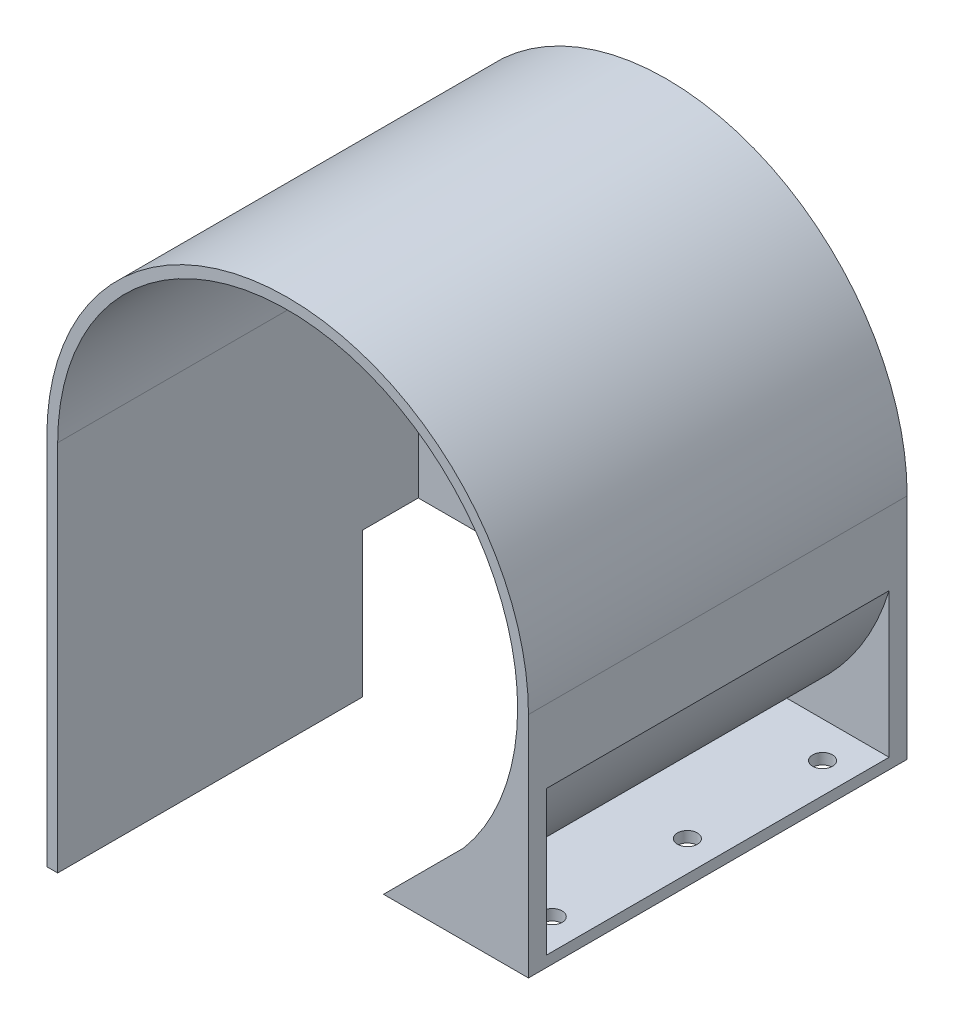
SolidWorks part; units mm, degrees
ref_plane "Front Plane" through (0, 0, 0) normal (0, 0, 1) x (1, 0, 0)
ref_plane "Top Plane" through (0, 0, 0) normal (0, 1, 0) x (1, 0, 0)
ref_plane "Right Plane" through (0, 0, 0) normal (1, 0, 0) x (0, 0, -1)
sketch "Sketch1" plane through (0, 0, 0) normal (0, 0, 1) x (1, 0, 0)
  line L0 (0, 0) -> (31.75, 0) construction
  line L1 (-34.925, 0) -> (-34.925, -63.5)
  line L4 (98.425, -64.8339) -> (98.425, 0)
  line L7 (-34.925, -63.5) -> (-34.925, -103.175)
  line L8 (-34.925, -103.175) -> (98.425, -103.175)
  line L9 (98.425, -64.8339) -> (98.425, -103.175)
  line L10 (-34.925, -63.5) -> (98.425, -103.175) construction
  line L11 (-34.925, -103.175) -> (98.425, -64.8339) construction
  circle A0 centre (0, 0) radius 25.4 construction
  circle A2 centre (31.75, 0) radius 63.5 construction
  arc A3 (98.425, 0) -> (-34.925, 0) centre (31.75, 0) ccw
  circle A4 centre (31.75, 0) radius 66.675 construction
  point P16 (32.89, -83.6767)
  dimension "D1" = 50.8
  dimension "D3" = 127
  dimension "D4" = 31.75
  dimension "D5" = 3.175
extrude "Boss-Extrude1" add sketch "Sketch1" along normal blind 104.85
sketch "Sketch2" plane through (0, 0, 104.85) normal (0, 0, 1) x (1, 0, 0)
  line L0 (31.75, -66.675) -> (31.75, -103.175)
  line L1 (-34.925, -103.175) -> (98.425, -103.175) construction
  line L2 (31.75, -103.175) -> (98.425, -103.175)
  line L3 (98.425, -103.175) -> (98.425, 0)
  arc A0 (31.75, -66.675) -> (98.425, 0) centre (31.75, 0) ccw
extrude "Cut-Extrude1" cut sketch "Sketch2" against normal up to next
sketch "Sketch3" plane through (0, 0, 0) normal (0, 0, -1) x (-1, 0, 0)
  line L0 (-31.75, -93.175) -> (34.925, -93.175) construction
  line L1 (-31.75, -103.175) -> (-31.75, -66.675) construction
  line L2 (34.925, 0) -> (34.925, -103.175) construction
  line L3 (-31.75, -73.175) -> (34.925, -73.175) construction
  line L4 (34.925, -103.175) -> (-31.75, -103.175) construction
  line L5 (1.5875, -93.175) -> (1.5875, -73.175) construction
  line L6 (1.5875, -83.175) -> (-26.4696, -83.175) construction
  circle A0 centre (-21.75, -93.175) radius 2.665
  circle A1 centre (-21.75, -73.175) radius 2.665
  circle A2 centre (24.925, -93.175) radius 2.665
  circle A3 centre (24.925, -73.175) radius 2.665
  dimension "D3" = 5.33
  dimension "D4" = 10
  dimension "D1" = 20
  dimension "D2" = 10
extrude "Cut-Extrude2" cut sketch "Sketch3" against normal up to next
sketch "Sketch5" plane through (0, 0, 0) normal (0, 0, -1) x (-1, 0, 0)
  line L0 (-31.75, -66.675) -> (-98.425, -66.675)
  line L1 (-98.425, -66.675) -> (-98.425, 0)
  arc A0 (34.925, 0) -> (-31.75, -66.675) centre (-31.75, 0) ccw construction
  arc A1 (-98.425, 0) -> (-31.75, -66.675) centre (-31.75, 0) ccw
extrude "Boss-Extrude2" add sketch "Sketch5" against normal up to surface (104.85 mm away) up to face at (24.415, -73.175, 104.85)
sketch "Sketch6" plane through (0, 0, 0) normal (0, 0, -1) x (-1, 0, 0)
  line L1 (-31.75, -66.675) -> (34.925, -66.675)
  line L2 (-31.75, -66.675) -> (-31.75, -103.175)
  line L3 (-31.75, -103.175) -> (34.925, -103.175)
  line L4 (34.925, -66.675) -> (34.925, -103.175)
  line L5 (-31.75, -66.675) -> (34.925, -103.175) construction
  line L6 (-31.75, -103.175) -> (34.925, -66.675) construction
  point P4 (1.5875, -84.925)
extrude "Cut-Extrude3" cut sketch "Sketch6" against normal up to next
sketch "Sketch7" plane through (0, -66.675, 0) normal (0, -1, 0) x (1, 0, 0)
  line L4 (98.425, 0) -> (98.425, 104.85)
  line L5 (98.425, 104.85) -> (-34.925, 104.85)
  line L6 (-34.925, 104.85) -> (-34.925, 0)
  line L7 (-34.925, 0) -> (98.425, 0)
  line L8 (98.425, 0) -> (98.425, 104.85)
  line L9 (98.425, 104.85) -> (-34.925, 104.85)
  line L10 (-34.925, 104.85) -> (-34.925, 0)
  line L11 (-34.925, 0) -> (98.425, 0)
  dimension "D1" = 0
extrude "Cut-Extrude4" cut sketch "Sketch7" against normal blind 3.5
ref_plane "Plane1" through (0, 0, 5) normal (0, 0, -1) x (-1, 0, 0)
sketch "Sketch8" plane through (0, 0, 5) normal (0, 0, -1) x (-1, 0, 0)
  line L1 (-98.425, -60.175) -> (-98.425, 0)
  line L2 (-98.425, -60.175) -> (34.925, -60.175)
  line L3 (-98.425, -60.175) -> (-66.8723, -60.175)
  arc A1 (-98.425, -20.225) -> (-66.8723, -60.175) centre (-31.75, 0) ccw
  dimension "D2" = 3
extrude "Cut-Extrude5" cut sketch "Sketch8" against normal offset from surface (94.85 mm away) 5 contours A1 L1 L3 region at (89.2304, -48.7887, 5) up to face at (31.75, -14.9188, 104.85)
sketch "Sketch9" plane through (0, -60.175, 0) normal (0, 1, 0) x (1, 0, 0)
  line L0 (100, 0) -> (100, -950) construction
  line L1 (100, 0) -> (100, -950) construction
  line L2 (90, -99.85) -> (90, -5) construction
  line L3 (98.425, -99.85) -> (66.8723, -99.85) construction
  line L4 (98.425, -5) -> (66.8723, -5) construction
  circle A0 centre (90, -89.85) radius 2.75
  circle A1 centre (90, -15) radius 2.75
  circle A2 centre (90, -52.425) radius 2.75
  dimension "D2" = 10
  dimension "D4" = 5.5
  dimension "D1" = 10
  dimension "D3" = 10
extrude "Cut-Extrude6" cut sketch "Sketch9" against normal blind 5
sketch "Sketch10" plane through (0, 0, 104.85) normal (0, 0, 1) x (1, 0, 0)
  line L0 (80.5279, -40.9295) -> (58.2824, -63.175)
  line L1 (98.425, -63.175) -> (-34.925, -63.175) construction
  line L2 (58.2824, -63.175) -> (31.75, -63.175)
  line L3 (-31.925, 0) -> (-31.925, -63.175)
  line L4 (-31.925, -63.175) -> (31.75, -63.175)
  arc A2 (95.425, 0) -> (-31.925, 0) centre (31.75, 0) ccw
  arc A3 (95.425, 0) -> (-31.925, 0) centre (31.75, 0) ccw
  arc A4 (80.5279, -40.9295) -> (-31.925, 0) centre (31.75, 0) ccw
  line M4 (-34.925, -63.175) -> (98.425, -63.175)
  dimension "D2" = 45
  dimension "D1" = 3
extrude "Cut-Extrude7" cut sketch "Sketch10" against normal offset from surface (99.85 mm away) 5 contours L0 A4 A3 L3 M4 region at (28.7964, -3.2991, 104.85) up to face at (31.75, -14.9188, 0)
sketch "Sketch11" plane through (0, -63.175, 0) normal (0, -1, 0) x (1, 0, 0)
  line L0 (-31.925, 5) -> (-31.925, 104.85) construction
  line L1 (-34.925, 104.85) -> (-31.925, 104.85)
  line L2 (-34.925, 104.85) -> (-34.925, 20.5)
  line L3 (-34.925, 20.5) -> (-31.925, 20.5)
  line L4 (-31.925, 104.85) -> (-31.925, 20.5)
  line L5 (-34.925, 104.85) -> (-31.925, 20.5) construction
  line L6 (-34.925, 20.5) -> (-31.925, 104.85) construction
  line L7 (-34.925, 0) -> (98.425, 0) construction
  point P4 (-33.425, 62.675)
  dimension "D1" = 20.5
extrude "Boss-Extrude3" add sketch "Sketch11" along normal blind 40
